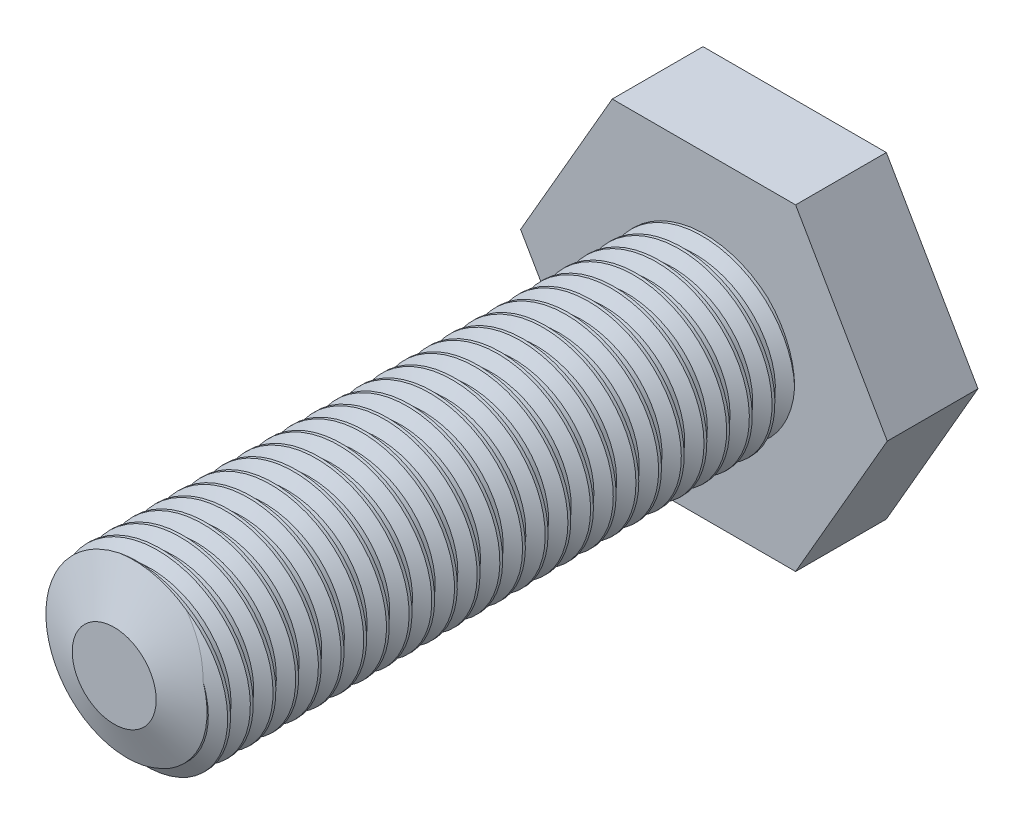
SolidWorks part; units mm, degrees
ref_plane "Top Plane" through (0, 0, 0) normal (0, 0, 1) x (1, 0, 0)
ref_plane "Front Plane" through (0, 0, 0) normal (0, 1, 0) x (1, 0, 0)
ref_plane "Right Plane" through (0, 0, 0) normal (1, 0, 0) x (0, 0, -1)
ref_plane "Top" through (0, 0, 0) normal (0, 0, 1) x (1, 0, 0)
ref_plane "Front" through (0, 0, 0) normal (0, 1, 0) x (1, 0, 0)
ref_plane "Right" through (0, 0, 0) normal (1, 0, 0) x (0, 0, -1)
ref_axis "X Axis" through (88.99, 0, 0) along (-1, 0, 0)
ref_axis "Y Axis" through (0, -55, 0) along (0, 1, 0)
ref_axis "Z Axis" through (0, 0, 55) along (0, 0, -1)
sketch "Sketch1" plane through (0, 0, 0) normal (0, 0, 1) x (1, 0, 0)
  line L1 (-4.0415, 7) -> (-8.0829, 0)
  line L2 (-8.0829, 0) -> (-4.0415, -7)
  line L3 (-4.0415, -7) -> (4.0415, -7)
  line L4 (4.0415, -7) -> (8.0829, 0)
  line L5 (8.0829, 0) -> (4.0415, 7)
  line L6 (4.0415, 7) -> (-4.0415, 7)
  circle A0 centre (0, 0) radius 7 construction
  dimension "D1" = 14
extrude "Boss-Extrude1" add sketch "Sketch1" along normal blind 30
sketch "Sketch3" plane through (0, 0, 30) normal (0, 0, 1) x (1, 0, 0)
  circle A0 centre (0, 0) radius 4
  dimension "D1" = 8
extrude "Cut-Extrude1" cut sketch "Sketch3" against normal offset from surface (26 mm away) 4 flip side to cut up to face at (0, 0, 0)
thread "Thread1" pitch 1 method cut trim with start face yes trim with end face yes profile "Thread Profile1" start angle 0, offset 1, length 0, pitch 1, diameter 8
ref_plane "Plane1" through (4, 0, 3) normal (0, -1, 0) x (1, 0, 0)
sketch "Thread Profile1" plane through (4, 0, 3) normal (0, -1, 0) x (1, 0, 0)
  line L0 (0, 0) -> (0, 1) construction
  line L11 (0, 0) -> (0, 0.875)
  line L12 (0, 0.875) -> (-0.5413, 0.5625)
  line L13 (-0.5413, 0.5625) -> (-0.5413, 0.3125)
  line L15 (-0.5413, 0.3125) -> (0, 0)
  line L17 (-0.5413, 0.4375) -> (0, 0.4375) construction
  point P2 (0, 0)
  dimension "Pitch" = 1
  dimension "Profile_Angle" = 60
  dimension "Profile_Land" = 0.25
  dimension "Profile_Height" = 0.5413
sketch "Sketch7" plane through (0, 0, 0) normal (0, 1, 0) x (1, 0, 0)
  line L0 (-1.4013, -30.1778) -> (-5.0139, -28.7487)
  line L1 (-5.0139, -28.7487) -> (-5.0139, -30.8725)
  line L2 (-5.0139, -30.8725) -> (-1.4013, -30.1778)
revolve "Cut-Revolve1" cut sketch "Sketch7" angle 360 about axis through (0, 0, -21.5992) along (0, 0, 1)
